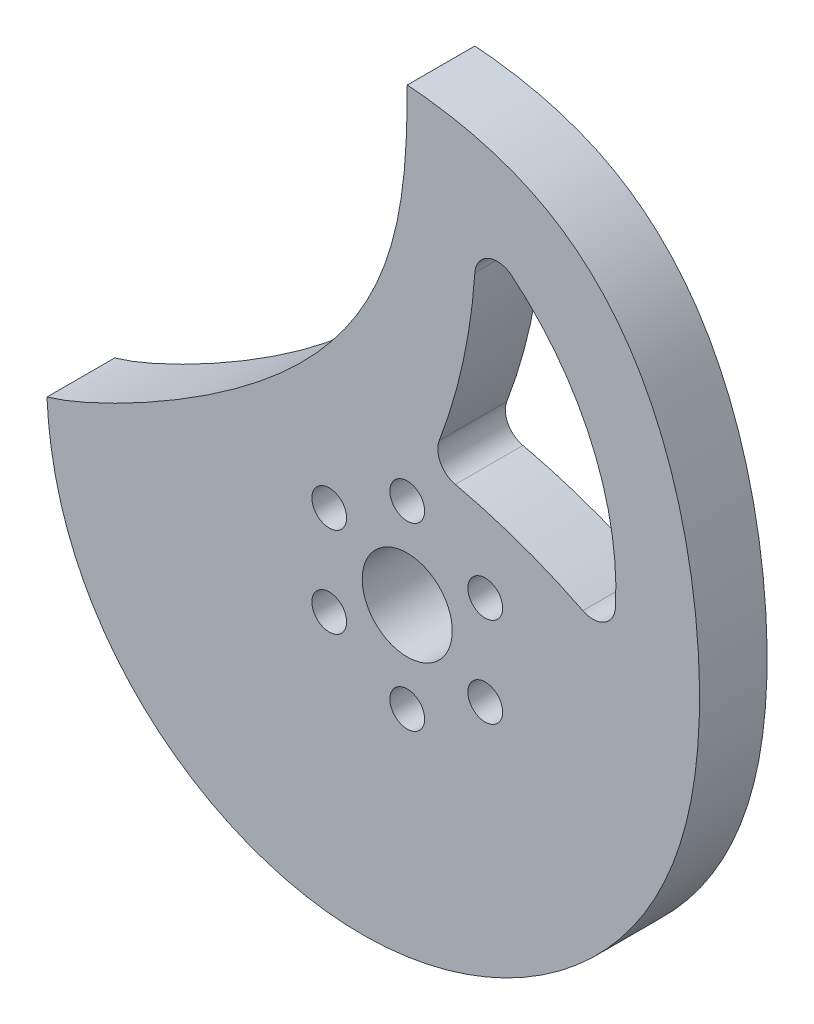
SolidWorks part; units mm, degrees
material "AISI Type A2 Tool Steel"
ref_plane "Front Plane" through (0, 0, 0) normal (0, 0, 1) x (1, 0, 0)
ref_plane "Top Plane" through (0, 0, 0) normal (0, 1, 0) x (1, 0, 0)
ref_plane "Right Plane" through (0, 0, 0) normal (1, 0, 0) x (0, 0, -1)
ref_plane "Plane1" through (0, 0, 0) normal (0, 0, -1) x (-1, 0, 0)
sketch "Sketch1" plane through (0, 0, 0) normal (0, 0, -1) x (-1, 0, 0)
  circle A0 centre (0, 0) radius 12.7
  arc A1 (-58.7073, 28.7043) -> (-29.4195, 95.1955) centre (21.1653, 33.2182) cw
  arc A2 (-29.4195, 95.1955) -> (-19.0686, 90.7021) centre (-25.4043, 90.2761) cw
  arc A3 (-19.0686, 90.7021) -> (-9.0222, 44.6754) centre (140.5708, 101.4375) ccw
  arc A4 (-9.0222, 44.6754) -> (-13.5611, 36.2285) centre (-14.9592, 42.4227) cw
  arc A5 (-13.5611, 36.2285) -> (-49.5252, 23.3842) centre (21.2545, -118.0273) ccw
  arc A6 (-49.5252, 23.3842) -> (-58.7073, 28.7043) centre (-52.3674, 29.0626) cw
  spline S0 degree 5 poles (101.6, 0) (101.3221, -6.1365) (99.9658, -17.9529) (95.5299, -34.3083) (85.0746, -53.2436) (65.9914, -71.4303) (42.9865, -83.3334) (18.2709, -88.3871) (-6.0804, -86.434) (-28.7704, -78.33) (-48.6255, -65.1605) (-64.5061, -47.9243) (-75.6549, -27.5607) (-81.729, -4.9389) (-83.305, 19.3723) (-81.4017, 44.6566) (-75.8896, 69.1059) (-66.5714, 90.7405) (-53.3534, 107.7515) (-36.9466, 119.0461) (-18.9813, 124.8162) (-7.108, 126.4503) (-1.8405, 126.9) (-0.2871, 127) (0, 127) knots -1 -1 -1 -1 -1 -1 -0.95 -0.9 -0.85 -0.8 -0.75 -0.7 -0.65 -0.6 -0.55 -0.5 -0.45 -0.4 -0.35 -0.3 -0.25 -0.2 -0.15 -0.1 -0.05 0 0 0 0 0 0
  spline S1 degree 5 poles (0, 127) (0, 125.4788) (0.0177, 122.257) (0.0972, 116.8859) (0.3989, 108.7197) (1.5971, 97.2581) (4.2051, 85.0941) (8.738, 72.808) (15.4433, 60.9012) (24.1564, 49.7136) (34.4456, 39.4692) (45.7073, 30.3015) (57.2694, 22.2807) (68.4816, 15.4341) (78.8164, 9.7638) (87.9482, 5.261) (94.1442, 2.5834) (98.1309, 1.0913) (100.4929, 0.3256) (101.6, 0) knots 0 0 0 0 0 0 0.066667 0.133333 0.2 0.266667 0.333333 0.4 0.466667 0.533333 0.6 0.666667 0.733333 0.8 0.866667 0.933333 1 1 1 1 1 1
extrude "Boss-Extrude1" add sketch "Sketch1" against normal blind 19.05
sketch "Sketch2" plane through (0, 0, 19.05) normal (0, 0, 1) x (1, 0, 0)
  circle A0 centre (0, 0) radius 25.4 construction
  circle A1 centre (0, 25.4) radius 4.9022
  circle A2 centre (21.997, 12.7) radius 4.9022
  circle A3 centre (21.997, -12.7) radius 4.9022
  circle A4 centre (0, -25.4) radius 4.9022
  circle A5 centre (-21.997, -12.7) radius 4.9022
  circle A6 centre (-21.997, 12.7) radius 4.9022
  point P17 (0, 0)
  dimension "D1" = 50.8
  dimension "D2" = 9.8044
  dimension "D3" = 6
extrude "Cut-Extrude1" cut sketch "Sketch2" against normal blind 19.05
